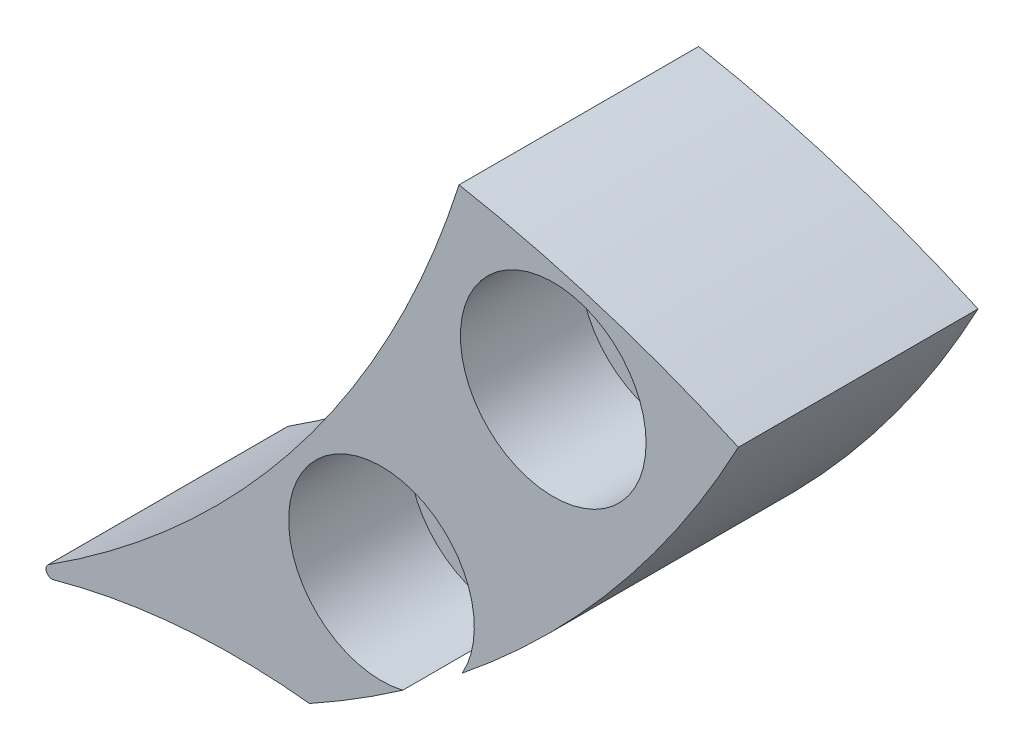
SolidWorks part; units mm, degrees
material "6061-T6 (SS)"
ref_plane "前视基准面" through (0, 0, 0) normal (0, 0, 1) x (1, 0, 0)
ref_plane "上视基准面" through (0, 0, 0) normal (0, 1, 0) x (1, 0, 0)
ref_plane "右视基准面" through (0, 0, 0) normal (1, 0, 0) x (0, 0, -1)
sketch "草图1" plane through (0, 0, 0) normal (0, 0, 1) x (1, 0, 0)
  line L0 (0, 0) -> (33, 0) construction
  line L1 (24, 0) -> (24, -50.1) construction
  line L2 (9, 4) -> (9, 0) construction
  line L3 (24, -50.1) -> (28.8621, -22.5254) construction
  line L4 (28.8621, -22.5254) -> (34.5979, -14.3339) construction
  arc A0 (17.753, -27.8178) -> (31.4527, -9.9864) centre (0, 0) ccw
  arc A1 (26.4587, -27.4832) -> (17.9141, -28.1791) centre (24, -50.1) ccw
  arc A2 (40.7809, -12.9107) -> (31.4527, -9.9864) centre (24, -50.1) ccw
  arc A3 (40.7809, -12.9107) -> (26.4587, -27.4832) centre (9, 4) cw
  circle A4 centre (34.5979, -14.3339) radius 1.75
  circle A5 centre (28.8621, -22.5254) radius 1.75
  arc A6 (17.753, -27.8178) -> (17.9141, -28.1791) centre (17.8606, -27.9864) ccw
  dimension "D2" = 45.5
  dimension "D4" = 33
  dimension "D5" = 81.6
  dimension "D8" = 36
  dimension "D12" = 3.5
  dimension "D14" = 0.2
  dimension "D1" = 24
  dimension "D3" = 50.1
  dimension "D6" = 4
  dimension "D7" = 9
  dimension "D9" = 10
  dimension "D10" = 28
  dimension "D11" = 25
  dimension "D13" = 10
extrude "凸台-拉伸1" add sketch "草图1" along normal blind 8
sketch "草图2" plane through (0, 0, 8) normal (0, 0, 1) x (1, 0, 0)
  circle A0 centre (28.8621, -22.5254) radius 3.1
  circle A1 centre (34.5979, -14.3339) radius 3.1
  dimension "D1" = 6.2
extrude "切除-拉伸1" cut sketch "草图2" against normal blind 4
